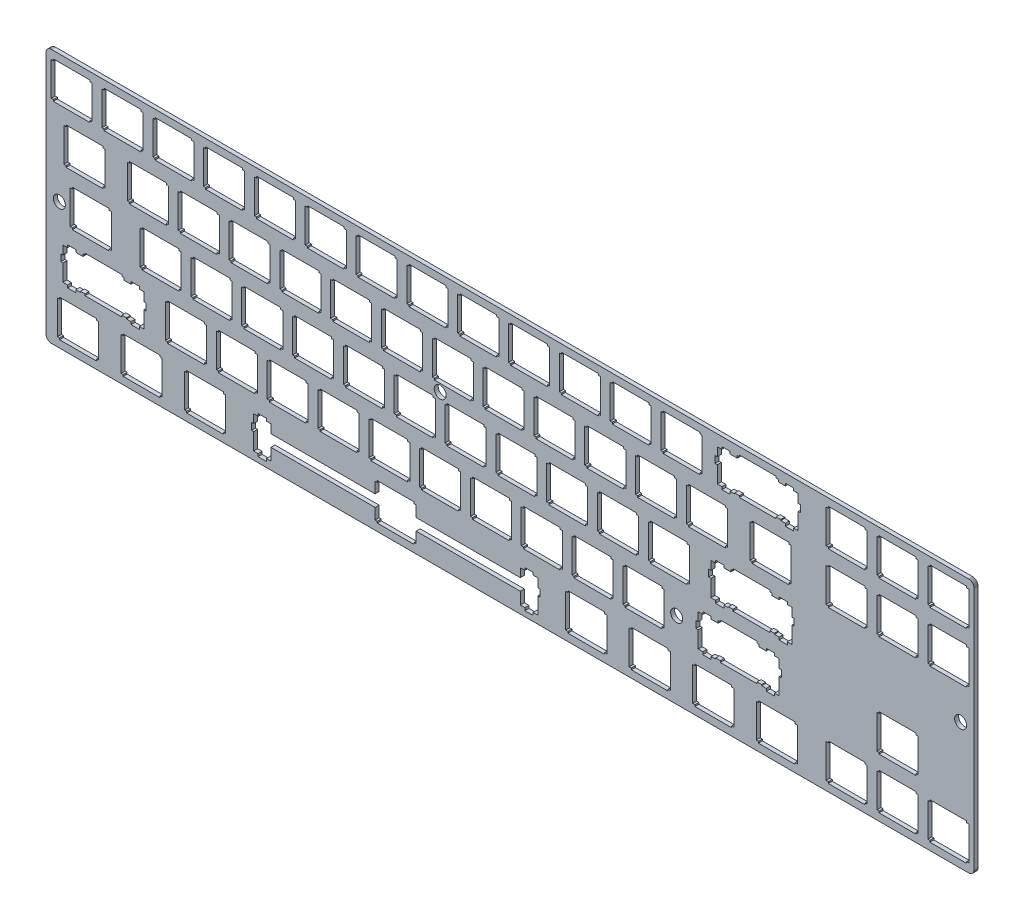
SolidWorks part; units mm, degrees
ref_plane "Front Plane" through (0, 0, 0) normal (0, 0, 1) x (1, 0, 0)
ref_plane "Top Plane" through (0, 0, 0) normal (0, 1, 0) x (1, 0, 0)
ref_plane "Right Plane" through (0, 0, 0) normal (1, 0, 0) x (0, 0, -1)
sketch "Model" plane through (0, 0, 0) normal (0, 0, 1) x (1, 0, 0)
  line L0 (345.958, 95.8603) -> (346.115, 95.8536)
  line L1 (346.115, 95.8536) -> (346.272, 95.8356)
  line L2 (346.272, 95.8356) -> (346.425, 95.8053)
  line L3 (346.425, 95.8053) -> (346.577, 95.7626)
  line L4 (346.577, 95.7626) -> (346.724, 95.7076)
  line L5 (346.724, 95.7076) -> (346.866, 95.6426)
  line L6 (346.866, 95.6426) -> (347.004, 95.5657)
  line L7 (347.004, 95.5657) -> (347.135, 95.4786)
  line L8 (347.135, 95.4786) -> (347.258, 95.3809)
  line L9 (347.258, 95.3809) -> (347.373, 95.2747)
  line L10 (347.373, 95.2747) -> (347.479, 95.159)
  line L11 (347.479, 95.159) -> (347.577, 95.0366)
  line L12 (347.577, 95.0366) -> (347.664, 94.9053)
  line L13 (347.664, 94.9053) -> (347.741, 94.7678)
  line L14 (347.741, 94.7678) -> (347.806, 94.6256)
  line L15 (347.806, 94.6256) -> (347.861, 94.4795)
  line L16 (347.861, 94.4795) -> (347.904, 94.3268)
  line L17 (347.904, 94.3268) -> (347.934, 94.1737)
  line L18 (347.934, 94.1737) -> (347.952, 94.0167)
  line L19 (347.952, 94.0167) -> (347.959, 93.8597)
  line L20 (347.959, 93.8597) -> (347.959, 2.4102)
  line L21 (347.959, 2.4102) -> (347.952, 2.2531)
  line L22 (347.952, 2.2531) -> (347.934, 2.0974)
  line L23 (347.934, 2.0974) -> (347.904, 1.943)
  line L24 (347.904, 1.943) -> (347.861, 1.7914)
  line L25 (347.861, 1.7914) -> (347.806, 1.644)
  line L26 (347.806, 1.644) -> (347.741, 1.5021)
  line L27 (347.741, 1.5021) -> (347.664, 1.3656)
  line L28 (347.664, 1.3656) -> (347.577, 1.2347)
  line L29 (347.577, 1.2347) -> (347.479, 1.1107)
  line L30 (347.479, 1.1107) -> (347.373, 0.9949)
  line L31 (347.373, 0.9949) -> (347.258, 0.8888)
  line L32 (347.258, 0.8888) -> (347.135, 0.791)
  line L33 (347.135, 0.791) -> (347.004, 0.7042)
  line L34 (347.004, 0.7042) -> (346.866, 0.627)
  line L35 (346.866, 0.627) -> (346.724, 0.5622)
  line L36 (346.724, 0.5622) -> (346.577, 0.5071)
  line L37 (346.577, 0.5071) -> (346.425, 0.4644)
  line L38 (346.425, 0.4644) -> (346.272, 0.4341)
  line L39 (346.272, 0.4341) -> (346.115, 0.4162)
  line L40 (346.115, 0.4162) -> (345.958, 0.4107)
  line L41 (345.958, 0.4107) -> (2.096, 0.4107)
  line L42 (2.096, 0.4107) -> (1.9389, 0.4162)
  line L43 (1.9389, 0.4162) -> (1.7818, 0.4341)
  line L44 (1.7818, 0.4341) -> (1.6288, 0.4644)
  line L45 (1.6288, 0.4644) -> (1.4759, 0.5071)
  line L46 (1.4759, 0.5071) -> (1.3298, 0.5622)
  line L47 (1.3298, 0.5622) -> (1.1879, 0.627)
  line L48 (1.1879, 0.627) -> (1.0501, 0.7042)
  line L49 (1.0501, 0.7042) -> (0.9192, 0.791)
  line L50 (0.9192, 0.791) -> (0.7965, 0.8888)
  line L51 (0.7965, 0.8888) -> (0.6808, 0.9949)
  line L52 (0.6808, 0.9949) -> (0.5746, 1.1107)
  line L53 (0.5746, 1.1107) -> (0.4768, 1.2347)
  line L54 (0.4768, 1.2347) -> (0.39, 1.3656)
  line L55 (0.39, 1.3656) -> (0.3128, 1.5021)
  line L56 (0.3128, 1.5021) -> (0.248, 1.644)
  line L57 (0.248, 1.644) -> (0.1929, 1.7914)
  line L58 (0.1929, 1.7914) -> (0.1502, 1.943)
  line L59 (0.1502, 1.943) -> (0.1199, 2.0974)
  line L60 (0.1199, 2.0974) -> (0.102, 2.2531)
  line L61 (0.102, 2.2531) -> (0.0951, 2.4088)
  line L62 (0.0951, 2.4088) -> (0.0951, 93.8597)
  line L63 (0.0951, 93.8597) -> (0.102, 94.0167)
  line L64 (0.102, 94.0167) -> (0.1199, 94.1737)
  line L65 (0.1199, 94.1737) -> (0.1502, 94.3268)
  line L66 (0.1502, 94.3268) -> (0.1929, 94.4795)
  line L67 (0.1929, 94.4795) -> (0.248, 94.6256)
  line L68 (0.248, 94.6256) -> (0.3128, 94.7678)
  line L69 (0.3128, 94.7678) -> (0.39, 94.9053)
  line L70 (0.39, 94.9053) -> (0.4768, 95.0366)
  line L71 (0.4768, 95.0366) -> (0.5746, 95.159)
  line L72 (0.5746, 95.159) -> (0.6808, 95.2747)
  line L73 (0.6808, 95.2747) -> (0.7965, 95.3809)
  line L74 (0.7965, 95.3809) -> (0.9192, 95.4786)
  line L75 (0.9192, 95.4786) -> (1.0501, 95.5657)
  line L76 (1.0501, 95.5657) -> (1.1879, 95.6426)
  line L77 (1.1879, 95.6426) -> (1.3298, 95.7076)
  line L78 (1.3298, 95.7076) -> (1.4759, 95.7626)
  line L79 (1.4759, 95.7626) -> (1.6288, 95.8053)
  line L80 (1.6288, 95.8053) -> (1.7818, 95.8356)
  line L81 (1.7818, 95.8356) -> (1.9389, 95.8536)
  line L82 (1.9389, 95.8536) -> (2.096, 95.8603)
  line L83 (2.096, 95.8603) -> (345.958, 95.8603)
  line L84 (124.263, 16.9361) -> (124.263, 16.3366)
  line L85 (124.263, 16.3366) -> (123.464, 16.3366)
  line L86 (123.464, 16.3366) -> (123.464, 12.2356)
  line L87 (123.464, 12.2356) -> (84.4381, 12.2356)
  line L88 (84.4381, 12.2356) -> (84.4381, 15.4657)
  line L89 (84.4381, 15.4657) -> (82.714, 15.4657)
  line L90 (82.714, 15.4657) -> (82.714, 16.3849)
  line L91 (82.714, 16.3849) -> (79.6135, 16.3849)
  line L92 (79.6135, 16.3849) -> (79.6135, 15.4657)
  line L93 (79.6135, 15.4657) -> (77.888, 15.4657)
  line L94 (77.888, 15.4657) -> (77.888, 12.2356)
  line L95 (77.888, 12.2356) -> (77.064, 12.2356)
  line L96 (77.064, 12.2356) -> (77.064, 9.6352)
  line L97 (77.064, 9.6352) -> (77.888, 9.6352)
  line L98 (77.888, 9.6352) -> (77.888, 3.3666)
  line L99 (77.888, 3.3666) -> (79.6135, 3.3666)
  line L100 (79.6135, 3.3666) -> (79.6135, 2.3854)
  line L101 (79.6135, 2.3854) -> (82.714, 2.3854)
  line L102 (82.714, 2.3854) -> (82.714, 3.3666)
  line L103 (82.714, 3.3666) -> (84.4381, 3.3666)
  line L104 (84.4381, 3.3666) -> (84.4381, 7.8355)
  line L105 (84.4381, 7.8355) -> (123.464, 7.8355)
  line L106 (123.464, 7.8355) -> (123.464, 3.7359)
  line L107 (123.464, 3.7359) -> (124.263, 3.7359)
  line L108 (124.263, 3.7359) -> (124.263, 3.135)
  line L109 (124.263, 3.135) -> (138.063, 3.135)
  line L110 (138.063, 3.135) -> (138.063, 3.7359)
  line L111 (138.063, 3.7359) -> (138.864, 3.7359)
  line L112 (138.864, 3.7359) -> (138.864, 7.8355)
  line L113 (138.864, 7.8355) -> (177.888, 7.8355)
  line L114 (177.888, 7.8355) -> (177.888, 3.3666)
  line L115 (177.888, 3.3666) -> (179.614, 3.3666)
  line L116 (179.614, 3.3666) -> (179.614, 2.3854)
  line L117 (179.614, 2.3854) -> (182.714, 2.3854)
  line L118 (182.714, 2.3854) -> (182.714, 3.3666)
  line L119 (182.714, 3.3666) -> (184.438, 3.3666)
  line L120 (184.438, 3.3666) -> (184.438, 9.6352)
  line L121 (184.438, 9.6352) -> (185.263, 9.6352)
  line L122 (185.263, 9.6352) -> (185.263, 12.2356)
  line L123 (185.263, 12.2356) -> (184.438, 12.2356)
  line L124 (184.438, 12.2356) -> (184.438, 15.4657)
  line L125 (184.438, 15.4657) -> (182.714, 15.4657)
  line L126 (182.714, 15.4657) -> (182.714, 16.3849)
  line L127 (182.714, 16.3849) -> (179.614, 16.3849)
  line L128 (179.614, 16.3849) -> (179.614, 15.4657)
  line L129 (179.614, 15.4657) -> (177.888, 15.4657)
  line L130 (177.888, 15.4657) -> (177.888, 12.2356)
  line L131 (177.888, 12.2356) -> (138.864, 12.2356)
  line L132 (138.864, 12.2356) -> (138.864, 16.3366)
  line L133 (138.864, 16.3366) -> (138.063, 16.3366)
  line L134 (138.063, 16.3366) -> (138.063, 16.9361)
  line L135 (138.063, 16.9361) -> (124.263, 16.9361)
  line L136 (331.432, 16.9361) -> (331.432, 16.3366)
  line L137 (331.432, 16.3366) -> (330.633, 16.3366)
  line L138 (330.633, 16.3366) -> (330.633, 3.7359)
  line L139 (330.633, 3.7359) -> (331.432, 3.7359)
  line L140 (331.432, 3.7359) -> (331.432, 3.135)
  line L141 (331.432, 3.135) -> (345.233, 3.135)
  line L142 (345.233, 3.135) -> (345.233, 3.7359)
  line L143 (345.233, 3.7359) -> (346.032, 3.7359)
  line L144 (346.032, 3.7359) -> (346.032, 16.3366)
  line L145 (346.032, 16.3366) -> (345.233, 16.3366)
  line L146 (345.233, 16.3366) -> (345.233, 16.9361)
  line L147 (345.233, 16.9361) -> (331.432, 16.9361)
  line L148 (312.382, 16.9361) -> (312.382, 16.3366)
  line L149 (312.382, 16.3366) -> (311.583, 16.3366)
  line L150 (311.583, 16.3366) -> (311.583, 3.7359)
  line L151 (311.583, 3.7359) -> (312.382, 3.7359)
  line L152 (312.382, 3.7359) -> (312.382, 3.135)
  line L153 (312.382, 3.135) -> (326.183, 3.135)
  line L154 (326.183, 3.135) -> (326.183, 3.7359)
  line L155 (326.183, 3.7359) -> (326.982, 3.7359)
  line L156 (326.982, 3.7359) -> (326.982, 16.3366)
  line L157 (326.982, 16.3366) -> (326.183, 16.3366)
  line L158 (326.183, 16.3366) -> (326.183, 16.9361)
  line L159 (326.183, 16.9361) -> (312.382, 16.9361)
  line L160 (293.332, 16.9361) -> (293.332, 16.3366)
  line L161 (293.332, 16.3366) -> (292.533, 16.3366)
  line L162 (292.533, 16.3366) -> (292.533, 3.7359)
  line L163 (292.533, 3.7359) -> (293.332, 3.7359)
  line L164 (293.332, 3.7359) -> (293.332, 3.135)
  line L165 (293.332, 3.135) -> (307.133, 3.135)
  line L166 (307.133, 3.135) -> (307.133, 3.7359)
  line L167 (307.133, 3.7359) -> (307.932, 3.7359)
  line L168 (307.932, 3.7359) -> (307.932, 16.3366)
  line L169 (307.932, 16.3366) -> (307.133, 16.3366)
  line L170 (307.133, 16.3366) -> (307.133, 16.9361)
  line L171 (307.133, 16.9361) -> (293.332, 16.9361)
  line L172 (267.138, 16.9361) -> (267.138, 16.3366)
  line L173 (267.138, 16.3366) -> (266.339, 16.3366)
  line L174 (266.339, 16.3366) -> (266.339, 3.7359)
  line L175 (266.339, 3.7359) -> (267.138, 3.7359)
  line L176 (267.138, 3.7359) -> (267.138, 3.135)
  line L177 (267.138, 3.135) -> (280.938, 3.135)
  line L178 (280.938, 3.135) -> (280.938, 3.7359)
  line L179 (280.938, 3.7359) -> (281.739, 3.7359)
  line L180 (281.739, 3.7359) -> (281.739, 16.3366)
  line L181 (281.739, 16.3366) -> (280.938, 16.3366)
  line L182 (280.938, 16.3366) -> (280.938, 16.9361)
  line L183 (280.938, 16.9361) -> (267.138, 16.9361)
  line L184 (243.327, 16.9361) -> (243.327, 16.3366)
  line L185 (243.327, 16.3366) -> (242.527, 16.3366)
  line L186 (242.527, 16.3366) -> (242.527, 3.7359)
  line L187 (242.527, 3.7359) -> (243.327, 3.7359)
  line L188 (243.327, 3.7359) -> (243.327, 3.135)
  line L189 (243.327, 3.135) -> (257.127, 3.135)
  line L190 (257.127, 3.135) -> (257.127, 3.7359)
  line L191 (257.127, 3.7359) -> (257.926, 3.7359)
  line L192 (257.926, 3.7359) -> (257.926, 16.3366)
  line L193 (257.926, 16.3366) -> (257.127, 16.3366)
  line L194 (257.127, 16.3366) -> (257.127, 16.9361)
  line L195 (257.127, 16.9361) -> (243.327, 16.9361)
  line L196 (219.513, 16.9361) -> (219.513, 16.3366)
  line L197 (219.513, 16.3366) -> (218.714, 16.3366)
  line L198 (218.714, 16.3366) -> (218.714, 3.7359)
  line L199 (218.714, 3.7359) -> (219.513, 3.7359)
  line L200 (219.513, 3.7359) -> (219.513, 3.135)
  line L201 (219.513, 3.135) -> (233.313, 3.135)
  line L202 (233.313, 3.135) -> (233.313, 3.7359)
  line L203 (233.313, 3.7359) -> (234.114, 3.7359)
  line L204 (234.114, 3.7359) -> (234.114, 16.3366)
  line L205 (234.114, 16.3366) -> (233.313, 16.3366)
  line L206 (233.313, 16.3366) -> (233.313, 16.9361)
  line L207 (233.313, 16.9361) -> (219.513, 16.9361)
  line L208 (195.702, 16.9361) -> (195.702, 16.3366)
  line L209 (195.702, 16.3366) -> (194.902, 16.3366)
  line L210 (194.902, 16.3366) -> (194.902, 3.7359)
  line L211 (194.902, 3.7359) -> (195.702, 3.7359)
  line L212 (195.702, 3.7359) -> (195.702, 3.135)
  line L213 (195.702, 3.135) -> (209.502, 3.135)
  line L214 (209.502, 3.135) -> (209.502, 3.7359)
  line L215 (209.502, 3.7359) -> (210.301, 3.7359)
  line L216 (210.301, 3.7359) -> (210.301, 16.3366)
  line L217 (210.301, 16.3366) -> (209.502, 16.3366)
  line L218 (209.502, 16.3366) -> (209.502, 16.9361)
  line L219 (209.502, 16.9361) -> (195.702, 16.9361)
  line L220 (52.8271, 16.9361) -> (52.8271, 16.3366)
  line L221 (52.8271, 16.3366) -> (52.0266, 16.3366)
  line L222 (52.0266, 16.3366) -> (52.0266, 3.7359)
  line L223 (52.0266, 3.7359) -> (52.8271, 3.7359)
  line L224 (52.8271, 3.7359) -> (52.8271, 3.135)
  line L225 (52.8271, 3.135) -> (66.6267, 3.135)
  line L226 (66.6267, 3.135) -> (66.6267, 3.7359)
  line L227 (66.6267, 3.7359) -> (67.4261, 3.7359)
  line L228 (67.4261, 3.7359) -> (67.4261, 16.3366)
  line L229 (67.4261, 16.3366) -> (66.6267, 16.3366)
  line L230 (66.6267, 16.3366) -> (66.6267, 16.9361)
  line L231 (66.6267, 16.9361) -> (52.8271, 16.9361)
  line L232 (29.0132, 16.9361) -> (29.0132, 16.3366)
  line L233 (29.0132, 16.3366) -> (28.214, 16.3366)
  line L234 (28.214, 16.3366) -> (28.214, 3.7359)
  line L235 (28.214, 3.7359) -> (29.0132, 3.7359)
  line L236 (29.0132, 3.7359) -> (29.0132, 3.135)
  line L237 (29.0132, 3.135) -> (42.8128, 3.135)
  line L238 (42.8128, 3.135) -> (42.8128, 3.7359)
  line L239 (42.8128, 3.7359) -> (43.6136, 3.7359)
  line L240 (43.6136, 3.7359) -> (43.6136, 16.3366)
  line L241 (43.6136, 16.3366) -> (42.8128, 16.3366)
  line L242 (42.8128, 16.3366) -> (42.8128, 16.9361)
  line L243 (42.8128, 16.9361) -> (29.0132, 16.9361)
  line L244 (5.2021, 16.9361) -> (5.2021, 16.3366)
  line L245 (5.2021, 16.3366) -> (4.4015, 16.3366)
  line L246 (4.4015, 16.3366) -> (4.4015, 3.7359)
  line L247 (4.4015, 3.7359) -> (5.2021, 3.7359)
  line L248 (5.2021, 3.7359) -> (5.2021, 3.135)
  line L249 (5.2021, 3.135) -> (19.0018, 3.135)
  line L250 (19.0018, 3.135) -> (19.0018, 3.7359)
  line L251 (19.0018, 3.7359) -> (19.801, 3.7359)
  line L252 (19.801, 3.7359) -> (19.801, 16.3366)
  line L253 (19.801, 16.3366) -> (19.0018, 16.3366)
  line L254 (19.0018, 16.3366) -> (19.0018, 16.9361)
  line L255 (19.0018, 16.9361) -> (5.2021, 16.9361)
  line L256 (252.851, 35.9876) -> (252.851, 35.3868)
  line L257 (252.851, 35.3868) -> (252.052, 35.3868)
  line L258 (252.052, 35.3868) -> (252.052, 34.5157)
  line L259 (267.451, 34.5157) -> (268.377, 34.5157)
  line L260 (272.214, 53.5658) -> (273.138, 53.5658)
  line L261 (251.127, 34.5157) -> (249.402, 34.5157)
  line L262 (249.402, 34.5157) -> (249.402, 35.4348)
  line L263 (249.402, 35.4348) -> (246.301, 35.4348)
  line L264 (246.301, 35.4348) -> (246.301, 34.5157)
  line L265 (246.301, 34.5157) -> (244.577, 34.5157)
  line L266 (244.577, 34.5157) -> (244.577, 31.2856)
  line L267 (244.577, 31.2856) -> (243.751, 31.2856)
  line L268 (243.751, 31.2856) -> (243.751, 28.6852)
  line L269 (243.751, 28.6852) -> (244.577, 28.6852)
  line L270 (244.577, 28.6852) -> (244.577, 22.4152)
  line L271 (244.577, 22.4152) -> (246.301, 22.4152)
  line L272 (246.301, 22.4152) -> (246.301, 21.4354)
  line L273 (246.301, 21.4354) -> (249.402, 21.4354)
  line L274 (249.402, 21.4354) -> (249.402, 22.4152)
  line L275 (249.402, 22.4152) -> (251.127, 22.4152)
  line L276 (251.127, 22.4152) -> (251.127, 22.7858)
  line L277 (29.326, 34.5157) -> (30.2521, 34.5157)
  line L279 (252.052, 22.7858) -> (252.851, 22.7858)
  line L280 (252.851, 22.7858) -> (252.851, 22.185)
  line L281 (252.851, 22.185) -> (266.652, 22.185)
  line L282 (266.652, 22.185) -> (266.652, 22.7858)
  line L283 (266.652, 22.7858) -> (267.451, 22.7858)
  line L286 (268.377, 22.7858) -> (268.377, 22.4152)
  line L287 (268.377, 22.4152) -> (270.101, 22.4152)
  line L288 (270.101, 22.4152) -> (270.101, 21.4354)
  line L289 (270.101, 21.4354) -> (273.202, 21.4354)
  line L290 (273.202, 21.4354) -> (273.202, 22.4152)
  line L291 (273.202, 22.4152) -> (274.927, 22.4152)
  line L292 (274.927, 22.4152) -> (274.927, 28.6852)
  line L293 (274.927, 28.6852) -> (275.751, 28.6852)
  line L294 (275.751, 28.6852) -> (275.751, 31.2856)
  line L295 (275.751, 31.2856) -> (274.927, 31.2856)
  line L296 (274.927, 31.2856) -> (274.927, 34.5157)
  line L297 (274.927, 34.5157) -> (273.202, 34.5157)
  line L298 (273.202, 34.5157) -> (273.202, 35.4348)
  line L299 (273.202, 35.4348) -> (270.101, 35.4348)
  line L300 (270.101, 35.4348) -> (270.101, 34.5157)
  line L301 (270.101, 34.5157) -> (268.377, 34.5157)
  line L304 (267.451, 34.5157) -> (267.451, 35.3868)
  line L305 (267.451, 35.3868) -> (266.652, 35.3868)
  line L306 (266.652, 35.3868) -> (266.652, 35.9876)
  line L307 (266.652, 35.9876) -> (252.851, 35.9876)
  line L308 (14.7271, 35.9876) -> (14.7271, 35.3868)
  line L309 (14.7271, 35.3868) -> (13.9265, 35.3868)
  line L310 (13.9265, 35.3868) -> (13.9265, 34.5157)
  line L313 (13.0018, 34.5157) -> (11.2765, 34.5157)
  line L314 (11.2765, 34.5157) -> (11.2765, 35.4348)
  line L315 (11.2765, 35.4348) -> (8.1759, 35.4348)
  line L316 (8.1759, 35.4348) -> (8.1759, 34.5157)
  line L317 (8.1759, 34.5157) -> (6.452, 34.5157)
  line L318 (6.452, 34.5157) -> (6.452, 31.2856)
  line L319 (6.452, 31.2856) -> (5.6265, 31.2856)
  line L320 (5.6265, 31.2856) -> (5.6265, 28.6852)
  line L321 (5.6265, 28.6852) -> (6.452, 28.6852)
  line L322 (6.452, 28.6852) -> (6.452, 22.4152)
  line L323 (6.452, 22.4152) -> (8.1759, 22.4152)
  line L324 (8.1759, 22.4152) -> (8.1759, 21.4354)
  line L325 (8.1759, 21.4354) -> (11.2765, 21.4354)
  line L326 (11.2765, 21.4354) -> (11.2765, 22.4152)
  line L327 (11.2765, 22.4152) -> (13.0018, 22.4152)
  line L328 (13.0018, 22.4152) -> (13.0018, 22.7858)
  line L331 (13.9265, 22.7858) -> (14.7271, 22.7858)
  line L332 (14.7271, 22.7858) -> (14.7271, 22.185)
  line L333 (14.7271, 22.185) -> (28.5268, 22.185)
  line L334 (28.5268, 22.185) -> (28.5268, 22.7858)
  line L335 (28.5268, 22.7858) -> (29.326, 22.7858)
  line L338 (30.2521, 22.7858) -> (30.2521, 22.4152)
  line L339 (30.2521, 22.4152) -> (31.976, 22.4152)
  line L340 (31.976, 22.4152) -> (31.976, 21.4354)
  line L341 (31.976, 21.4354) -> (35.0766, 21.4354)
  line L342 (35.0766, 21.4354) -> (35.0766, 22.4152)
  line L343 (35.0766, 22.4152) -> (36.8018, 22.4152)
  line L344 (36.8018, 22.4152) -> (36.8018, 28.6852)
  line L345 (36.8018, 28.6852) -> (37.6259, 28.6852)
  line L346 (37.6259, 28.6852) -> (37.6259, 31.2856)
  line L347 (37.6259, 31.2856) -> (36.8018, 31.2856)
  line L348 (36.8018, 31.2856) -> (36.8018, 34.5157)
  line L349 (36.8018, 34.5157) -> (35.0766, 34.5157)
  line L350 (35.0766, 34.5157) -> (35.0766, 35.4348)
  line L351 (35.0766, 35.4348) -> (31.976, 35.4348)
  line L352 (31.976, 35.4348) -> (31.976, 34.5157)
  line L353 (31.976, 34.5157) -> (30.2521, 34.5157)
  line L356 (29.326, 34.5157) -> (29.326, 35.3868)
  line L357 (29.326, 35.3868) -> (28.5268, 35.3868)
  line L358 (28.5268, 35.3868) -> (28.5268, 35.9876)
  line L359 (28.5268, 35.9876) -> (14.7271, 35.9876)
  line L360 (312.382, 35.9876) -> (312.382, 35.3868)
  line L361 (312.382, 35.3868) -> (311.583, 35.3868)
  line L362 (311.583, 35.3868) -> (311.583, 22.7858)
  line L363 (311.583, 22.7858) -> (312.382, 22.7858)
  line L364 (312.382, 22.7858) -> (312.382, 22.185)
  line L365 (312.382, 22.185) -> (326.183, 22.185)
  line L366 (326.183, 22.185) -> (326.183, 22.7858)
  line L367 (326.183, 22.7858) -> (326.982, 22.7858)
  line L368 (326.982, 22.7858) -> (326.982, 35.3868)
  line L369 (326.982, 35.3868) -> (326.183, 35.3868)
  line L370 (326.183, 35.3868) -> (326.183, 35.9876)
  line L371 (326.183, 35.9876) -> (312.382, 35.9876)
  line L372 (217.132, 35.9876) -> (217.132, 35.3868)
  line L373 (217.132, 35.3868) -> (216.333, 35.3868)
  line L374 (216.333, 35.3868) -> (216.333, 22.7858)
  line L375 (216.333, 22.7858) -> (217.132, 22.7858)
  line L376 (217.132, 22.7858) -> (217.132, 22.185)
  line L377 (217.132, 22.185) -> (230.933, 22.185)
  line L378 (230.933, 22.185) -> (230.933, 22.7858)
  line L379 (230.933, 22.7858) -> (231.732, 22.7858)
  line L380 (231.732, 22.7858) -> (231.732, 35.3868)
  line L381 (231.732, 35.3868) -> (230.933, 35.3868)
  line L382 (230.933, 35.3868) -> (230.933, 35.9876)
  line L383 (230.933, 35.9876) -> (217.132, 35.9876)
  line L384 (198.082, 35.9876) -> (198.082, 35.3868)
  line L385 (198.082, 35.3868) -> (197.283, 35.3868)
  line L386 (197.283, 35.3868) -> (197.283, 22.7858)
  line L387 (197.283, 22.7858) -> (198.082, 22.7858)
  line L388 (198.082, 22.7858) -> (198.082, 22.185)
  line L389 (198.082, 22.185) -> (211.883, 22.185)
  line L390 (211.883, 22.185) -> (211.883, 22.7858)
  line L391 (211.883, 22.7858) -> (212.682, 22.7858)
  line L392 (212.682, 22.7858) -> (212.682, 35.3868)
  line L393 (212.682, 35.3868) -> (211.883, 35.3868)
  line L394 (211.883, 35.3868) -> (211.883, 35.9876)
  line L395 (211.883, 35.9876) -> (198.082, 35.9876)
  line L396 (179.032, 35.9876) -> (179.032, 35.3868)
  line L397 (179.032, 35.3868) -> (178.233, 35.3868)
  line L398 (178.233, 35.3868) -> (178.233, 22.7858)
  line L399 (178.233, 22.7858) -> (179.032, 22.7858)
  line L400 (179.032, 22.7858) -> (179.032, 22.185)
  line L401 (179.032, 22.185) -> (192.833, 22.185)
  line L402 (192.833, 22.185) -> (192.833, 22.7858)
  line L403 (192.833, 22.7858) -> (193.632, 22.7858)
  line L404 (193.632, 22.7858) -> (193.632, 35.3868)
  line L405 (193.632, 35.3868) -> (192.833, 35.3868)
  line L406 (192.833, 35.3868) -> (192.833, 35.9876)
  line L407 (192.833, 35.9876) -> (179.032, 35.9876)
  line L408 (159.982, 35.9876) -> (159.982, 35.3868)
  line L409 (159.982, 35.3868) -> (159.183, 35.3868)
  line L410 (159.183, 35.3868) -> (159.183, 22.7858)
  line L411 (159.183, 22.7858) -> (159.982, 22.7858)
  line L412 (159.982, 22.7858) -> (159.982, 22.185)
  line L413 (159.982, 22.185) -> (173.783, 22.185)
  line L414 (173.783, 22.185) -> (173.783, 22.7858)
  line L415 (173.783, 22.7858) -> (174.582, 22.7858)
  line L416 (174.582, 22.7858) -> (174.582, 35.3868)
  line L417 (174.582, 35.3868) -> (173.783, 35.3868)
  line L418 (173.783, 35.3868) -> (173.783, 35.9876)
  line L419 (173.783, 35.9876) -> (159.982, 35.9876)
  line L420 (140.932, 35.9876) -> (140.932, 35.3868)
  line L421 (140.932, 35.3868) -> (140.133, 35.3868)
  line L422 (140.133, 35.3868) -> (140.133, 22.7858)
  line L423 (140.133, 22.7858) -> (140.932, 22.7858)
  line L424 (140.932, 22.7858) -> (140.932, 22.185)
  line L425 (140.932, 22.185) -> (154.733, 22.185)
  line L426 (154.733, 22.185) -> (154.733, 22.7858)
  line L427 (154.733, 22.7858) -> (155.532, 22.7858)
  line L428 (155.532, 22.7858) -> (155.532, 35.3868)
  line L429 (155.532, 35.3868) -> (154.733, 35.3868)
  line L430 (154.733, 35.3868) -> (154.733, 35.9876)
  line L431 (154.733, 35.9876) -> (140.932, 35.9876)
  line L432 (121.882, 35.9876) -> (121.882, 35.3868)
  line L433 (121.882, 35.3868) -> (121.083, 35.3868)
  line L434 (121.083, 35.3868) -> (121.083, 22.7858)
  line L435 (121.083, 22.7858) -> (121.882, 22.7858)
  line L436 (121.882, 22.7858) -> (121.882, 22.185)
  line L437 (121.882, 22.185) -> (135.683, 22.185)
  line L438 (135.683, 22.185) -> (135.683, 22.7858)
  line L439 (135.683, 22.7858) -> (136.482, 22.7858)
  line L440 (136.482, 22.7858) -> (136.482, 35.3868)
  line L441 (136.482, 35.3868) -> (135.683, 35.3868)
  line L442 (135.683, 35.3868) -> (135.683, 35.9876)
  line L443 (135.683, 35.9876) -> (121.882, 35.9876)
  line L444 (102.832, 35.9876) -> (102.832, 35.3868)
  line L445 (102.832, 35.3868) -> (102.033, 35.3868)
  line L446 (102.033, 35.3868) -> (102.033, 22.7858)
  line L447 (102.033, 22.7858) -> (102.832, 22.7858)
  line L448 (102.832, 22.7858) -> (102.832, 22.185)
  line L449 (102.832, 22.185) -> (116.633, 22.185)
  line L450 (116.633, 22.185) -> (116.633, 22.7858)
  line L451 (116.633, 22.7858) -> (117.432, 22.7858)
  line L452 (117.432, 22.7858) -> (117.432, 35.3868)
  line L453 (117.432, 35.3868) -> (116.633, 35.3868)
  line L454 (116.633, 35.3868) -> (116.633, 35.9876)
  line L455 (116.633, 35.9876) -> (102.832, 35.9876)
  line L456 (83.7819, 35.9876) -> (83.7819, 35.3868)
  line L457 (83.7819, 35.3868) -> (82.9829, 35.3868)
  line L458 (82.9829, 35.3868) -> (82.9829, 22.7858)
  line L459 (82.9829, 22.7858) -> (83.7819, 22.7858)
  line L460 (83.7819, 22.7858) -> (83.7819, 22.185)
  line L461 (83.7819, 22.185) -> (97.5829, 22.185)
  line L462 (97.5829, 22.185) -> (97.5829, 22.7858)
  line L463 (97.5829, 22.7858) -> (98.3823, 22.7858)
  line L464 (98.3823, 22.7858) -> (98.3823, 35.3868)
  line L465 (98.3823, 35.3868) -> (97.5829, 35.3868)
  line L466 (97.5829, 35.3868) -> (97.5829, 35.9876)
  line L467 (97.5829, 35.9876) -> (83.7819, 35.9876)
  line L468 (64.7319, 35.9876) -> (64.7319, 35.3868)
  line L469 (64.7319, 35.3868) -> (63.9329, 35.3868)
  line L470 (63.9329, 35.3868) -> (63.9329, 22.7858)
  line L471 (63.9329, 22.7858) -> (64.7319, 22.7858)
  line L472 (64.7319, 22.7858) -> (64.7319, 22.185)
  line L473 (64.7319, 22.185) -> (78.5329, 22.185)
  line L474 (78.5329, 22.185) -> (78.5329, 22.7858)
  line L475 (78.5329, 22.7858) -> (79.3323, 22.7858)
  line L476 (79.3323, 22.7858) -> (79.3323, 35.3868)
  line L477 (79.3323, 35.3868) -> (78.5329, 35.3868)
  line L478 (78.5329, 35.3868) -> (78.5329, 35.9876)
  line L479 (78.5329, 35.9876) -> (64.7319, 35.9876)
  line L480 (45.6819, 35.9876) -> (45.6819, 35.3868)
  line L481 (45.6819, 35.3868) -> (44.8829, 35.3868)
  line L482 (44.8829, 35.3868) -> (44.8829, 22.7858)
  line L483 (44.8829, 22.7858) -> (45.6819, 22.7858)
  line L484 (45.6819, 22.7858) -> (45.6819, 22.185)
  line L485 (45.6819, 22.185) -> (59.4829, 22.185)
  line L486 (59.4829, 22.185) -> (59.4829, 22.7858)
  line L487 (59.4829, 22.7858) -> (60.2823, 22.7858)
  line L488 (60.2823, 22.7858) -> (60.2823, 35.3868)
  line L489 (60.2823, 35.3868) -> (59.4829, 35.3868)
  line L490 (59.4829, 35.3868) -> (59.4829, 35.9876)
  line L491 (59.4829, 35.9876) -> (45.6819, 35.9876)
  line L492 (257.613, 55.0362) -> (257.613, 54.4354)
  line L493 (257.613, 54.4354) -> (256.814, 54.4354)
  line L494 (256.814, 54.4354) -> (256.814, 53.5658)
  line L497 (255.888, 53.5658) -> (254.163, 53.5658)
  line L498 (254.163, 53.5658) -> (254.163, 54.4862)
  line L499 (254.163, 54.4862) -> (251.063, 54.4862)
  line L500 (251.063, 54.4862) -> (251.063, 53.5658)
  line L501 (251.063, 53.5658) -> (249.338, 53.5658)
  line L502 (249.338, 53.5658) -> (249.338, 50.3357)
  line L503 (249.338, 50.3357) -> (248.514, 50.3357)
  line L504 (248.514, 50.3357) -> (248.514, 47.7365)
  line L505 (248.514, 47.7365) -> (249.338, 47.7365)
  line L506 (249.338, 47.7365) -> (249.338, 41.4666)
  line L507 (249.338, 41.4666) -> (251.063, 41.4666)
  line L508 (251.063, 41.4666) -> (251.063, 40.4855)
  line L509 (251.063, 40.4855) -> (254.163, 40.4855)
  line L510 (254.163, 40.4855) -> (254.163, 41.4666)
  line L511 (254.163, 41.4666) -> (255.888, 41.4666)
  line L512 (255.888, 41.4666) -> (255.888, 41.8359)
  line L515 (256.814, 41.8359) -> (257.613, 41.8359)
  line L516 (257.613, 41.8359) -> (257.613, 41.2365)
  line L517 (257.613, 41.2365) -> (271.413, 41.2365)
  line L518 (271.413, 41.2365) -> (271.413, 41.8359)
  line L519 (271.413, 41.8359) -> (272.214, 41.8359)
  line L522 (273.138, 41.8359) -> (273.138, 41.4666)
  line L523 (273.138, 41.4666) -> (274.864, 41.4666)
  line L524 (274.864, 41.4666) -> (274.864, 40.4855)
  line L525 (274.864, 40.4855) -> (277.964, 40.4855)
  line L526 (277.964, 40.4855) -> (277.964, 41.4666)
  line L527 (277.964, 41.4666) -> (279.688, 41.4666)
  line L528 (279.688, 41.4666) -> (279.688, 47.7365)
  line L529 (279.688, 47.7365) -> (280.513, 47.7365)
  line L530 (280.513, 47.7365) -> (280.513, 50.3357)
  line L531 (280.513, 50.3357) -> (279.688, 50.3357)
  line L532 (279.688, 50.3357) -> (279.688, 53.5658)
  line L533 (279.688, 53.5658) -> (277.964, 53.5658)
  line L534 (277.964, 53.5658) -> (277.964, 54.4862)
  line L535 (277.964, 54.4862) -> (274.864, 54.4862)
  line L536 (274.864, 54.4862) -> (274.864, 53.5658)
  line L537 (274.864, 53.5658) -> (273.138, 53.5658)
  line L540 (272.214, 53.5658) -> (272.214, 54.4354)
  line L541 (272.214, 54.4354) -> (271.413, 54.4354)
  line L542 (271.413, 54.4354) -> (271.413, 55.0362)
  line L543 (271.413, 55.0362) -> (257.613, 55.0362)
  line L544 (226.657, 55.0362) -> (226.657, 54.4354)
  line L545 (226.657, 54.4354) -> (225.858, 54.4354)
  line L546 (225.858, 54.4354) -> (225.858, 41.8359)
  line L547 (225.858, 41.8359) -> (226.657, 41.8359)
  line L548 (226.657, 41.8359) -> (226.657, 41.2365)
  line L549 (226.657, 41.2365) -> (240.458, 41.2365)
  line L550 (240.458, 41.2365) -> (240.458, 41.8359)
  line L551 (240.458, 41.8359) -> (241.257, 41.8359)
  line L552 (241.257, 41.8359) -> (241.257, 54.4354)
  line L553 (241.257, 54.4354) -> (240.458, 54.4354)
  line L554 (240.458, 54.4354) -> (240.458, 55.0362)
  line L555 (240.458, 55.0362) -> (226.657, 55.0362)
  line L556 (207.607, 55.0362) -> (207.607, 54.4354)
  line L557 (207.607, 54.4354) -> (206.808, 54.4354)
  line L558 (206.808, 54.4354) -> (206.808, 41.8359)
  line L559 (206.808, 41.8359) -> (207.607, 41.8359)
  line L560 (207.607, 41.8359) -> (207.607, 41.2365)
  line L561 (207.607, 41.2365) -> (221.408, 41.2365)
  line L562 (221.408, 41.2365) -> (221.408, 41.8359)
  line L563 (221.408, 41.8359) -> (222.207, 41.8359)
  line L564 (222.207, 41.8359) -> (222.207, 54.4354)
  line L565 (222.207, 54.4354) -> (221.408, 54.4354)
  line L566 (221.408, 54.4354) -> (221.408, 55.0362)
  line L567 (221.408, 55.0362) -> (207.607, 55.0362)
  line L568 (188.557, 55.0362) -> (188.557, 54.4354)
  line L569 (188.557, 54.4354) -> (187.758, 54.4354)
  line L570 (187.758, 54.4354) -> (187.758, 41.8359)
  line L571 (187.758, 41.8359) -> (188.557, 41.8359)
  line L572 (188.557, 41.8359) -> (188.557, 41.2365)
  line L573 (188.557, 41.2365) -> (202.358, 41.2365)
  line L574 (202.358, 41.2365) -> (202.358, 41.8359)
  line L575 (202.358, 41.8359) -> (203.157, 41.8359)
  line L576 (203.157, 41.8359) -> (203.157, 54.4354)
  line L577 (203.157, 54.4354) -> (202.358, 54.4354)
  line L578 (202.358, 54.4354) -> (202.358, 55.0362)
  line L579 (202.358, 55.0362) -> (188.557, 55.0362)
  line L580 (169.507, 55.0362) -> (169.507, 54.4354)
  line L581 (169.507, 54.4354) -> (168.708, 54.4354)
  line L582 (168.708, 54.4354) -> (168.708, 41.8359)
  line L583 (168.708, 41.8359) -> (169.507, 41.8359)
  line L584 (169.507, 41.8359) -> (169.507, 41.2365)
  line L585 (169.507, 41.2365) -> (183.308, 41.2365)
  line L586 (183.308, 41.2365) -> (183.308, 41.8359)
  line L587 (183.308, 41.8359) -> (184.107, 41.8359)
  line L588 (184.107, 41.8359) -> (184.107, 54.4354)
  line L589 (184.107, 54.4354) -> (183.308, 54.4354)
  line L590 (183.308, 54.4354) -> (183.308, 55.0362)
  line L591 (183.308, 55.0362) -> (169.507, 55.0362)
  line L592 (150.457, 55.0362) -> (150.457, 54.4354)
  line L593 (150.457, 54.4354) -> (149.658, 54.4354)
  line L594 (149.658, 54.4354) -> (149.658, 41.8359)
  line L595 (149.658, 41.8359) -> (150.457, 41.8359)
  line L596 (150.457, 41.8359) -> (150.457, 41.2365)
  line L597 (150.457, 41.2365) -> (164.258, 41.2365)
  line L598 (164.258, 41.2365) -> (164.258, 41.8359)
  line L599 (164.258, 41.8359) -> (165.057, 41.8359)
  line L600 (165.057, 41.8359) -> (165.057, 54.4354)
  line L601 (165.057, 54.4354) -> (164.258, 54.4354)
  line L602 (164.258, 54.4354) -> (164.258, 55.0362)
  line L603 (164.258, 55.0362) -> (150.457, 55.0362)
  line L604 (131.407, 55.0362) -> (131.407, 54.4354)
  line L605 (131.407, 54.4354) -> (130.608, 54.4354)
  line L606 (130.608, 54.4354) -> (130.608, 41.8359)
  line L607 (130.608, 41.8359) -> (131.407, 41.8359)
  line L608 (131.407, 41.8359) -> (131.407, 41.2365)
  line L609 (131.407, 41.2365) -> (145.208, 41.2365)
  line L610 (145.208, 41.2365) -> (145.208, 41.8359)
  line L611 (145.208, 41.8359) -> (146.007, 41.8359)
  line L612 (146.007, 41.8359) -> (146.007, 54.4354)
  line L613 (146.007, 54.4354) -> (145.208, 54.4354)
  line L614 (145.208, 54.4354) -> (145.208, 55.0362)
  line L615 (145.208, 55.0362) -> (131.407, 55.0362)
  line L616 (112.357, 55.0362) -> (112.357, 54.4354)
  line L617 (112.357, 54.4354) -> (111.558, 54.4354)
  line L618 (111.558, 54.4354) -> (111.558, 41.8359)
  line L619 (111.558, 41.8359) -> (112.357, 41.8359)
  line L620 (112.357, 41.8359) -> (112.357, 41.2365)
  line L621 (112.357, 41.2365) -> (126.158, 41.2365)
  line L622 (126.158, 41.2365) -> (126.158, 41.8359)
  line L623 (126.158, 41.8359) -> (126.957, 41.8359)
  line L624 (126.957, 41.8359) -> (126.957, 54.4354)
  line L625 (126.957, 54.4354) -> (126.158, 54.4354)
  line L626 (126.158, 54.4354) -> (126.158, 55.0362)
  line L627 (126.158, 55.0362) -> (112.357, 55.0362)
  line L628 (93.3069, 55.0362) -> (93.3069, 54.4354)
  line L629 (93.3069, 54.4354) -> (92.5079, 54.4354)
  line L630 (92.5079, 54.4354) -> (92.5079, 41.8359)
  line L631 (92.5079, 41.8359) -> (93.3069, 41.8359)
  line L632 (93.3069, 41.8359) -> (93.3069, 41.2365)
  line L633 (93.3069, 41.2365) -> (107.108, 41.2365)
  line L634 (107.108, 41.2365) -> (107.108, 41.8359)
  line L635 (107.108, 41.8359) -> (107.907, 41.8359)
  line L636 (107.907, 41.8359) -> (107.907, 54.4354)
  line L637 (107.907, 54.4354) -> (107.108, 54.4354)
  line L638 (107.108, 54.4354) -> (107.108, 55.0362)
  line L639 (107.108, 55.0362) -> (93.3069, 55.0362)
  line L640 (74.2569, 55.0362) -> (74.2569, 54.4354)
  line L641 (74.2569, 54.4354) -> (73.4579, 54.4354)
  line L642 (73.4579, 54.4354) -> (73.4579, 41.8359)
  line L643 (73.4579, 41.8359) -> (74.2569, 41.8359)
  line L644 (74.2569, 41.8359) -> (74.2569, 41.2365)
  line L645 (74.2569, 41.2365) -> (88.0579, 41.2365)
  line L646 (88.0579, 41.2365) -> (88.0579, 41.8359)
  line L647 (88.0579, 41.8359) -> (88.8573, 41.8359)
  line L648 (88.8573, 41.8359) -> (88.8573, 54.4354)
  line L649 (88.8573, 54.4354) -> (88.0579, 54.4354)
  line L650 (88.0579, 54.4354) -> (88.0579, 55.0362)
  line L651 (88.0579, 55.0362) -> (74.2569, 55.0362)
  line L652 (55.2069, 55.0362) -> (55.2069, 54.4354)
  line L653 (55.2069, 54.4354) -> (54.4079, 54.4354)
  line L654 (54.4079, 54.4354) -> (54.4079, 41.8359)
  line L655 (54.4079, 41.8359) -> (55.2069, 41.8359)
  line L656 (55.2069, 41.8359) -> (55.2069, 41.2365)
  line L657 (55.2069, 41.2365) -> (69.0079, 41.2365)
  line L658 (69.0079, 41.2365) -> (69.0079, 41.8359)
  line L659 (69.0079, 41.8359) -> (69.8073, 41.8359)
  line L660 (69.8073, 41.8359) -> (69.8073, 54.4354)
  line L661 (69.8073, 54.4354) -> (69.0079, 54.4354)
  line L662 (69.0079, 54.4354) -> (69.0079, 55.0362)
  line L663 (69.0079, 55.0362) -> (55.2069, 55.0362)
  line L664 (36.1569, 55.0362) -> (36.1569, 54.4354)
  line L665 (36.1569, 54.4354) -> (35.3579, 54.4354)
  line L666 (35.3579, 54.4354) -> (35.3579, 41.8359)
  line L667 (35.3579, 41.8359) -> (36.1569, 41.8359)
  line L668 (36.1569, 41.8359) -> (36.1569, 41.2365)
  line L669 (36.1569, 41.2365) -> (49.9579, 41.2365)
  line L670 (49.9579, 41.2365) -> (49.9579, 41.8359)
  line L671 (49.9579, 41.8359) -> (50.7573, 41.8359)
  line L672 (50.7573, 41.8359) -> (50.7573, 54.4354)
  line L673 (50.7573, 54.4354) -> (49.9579, 54.4354)
  line L674 (49.9579, 54.4354) -> (49.9579, 55.0362)
  line L675 (49.9579, 55.0362) -> (36.1569, 55.0362)
  line L676 (9.9632, 55.0362) -> (9.9632, 54.4354)
  line L677 (9.9632, 54.4354) -> (9.164, 54.4354)
  line L678 (9.164, 54.4354) -> (9.164, 41.8359)
  line L679 (9.164, 41.8359) -> (9.9632, 41.8359)
  line L680 (9.9632, 41.8359) -> (9.9632, 41.2365)
  line L681 (9.9632, 41.2365) -> (23.7629, 41.2365)
  line L682 (23.7629, 41.2365) -> (23.7629, 41.8359)
  line L683 (23.7629, 41.8359) -> (24.5635, 41.8359)
  line L684 (24.5635, 41.8359) -> (24.5635, 54.4354)
  line L685 (24.5635, 54.4354) -> (23.7629, 54.4354)
  line L686 (23.7629, 54.4354) -> (23.7629, 55.0362)
  line L687 (23.7629, 55.0362) -> (9.9632, 55.0362)
  line L688 (331.432, 74.0847) -> (331.432, 73.4868)
  line L689 (331.432, 73.4868) -> (330.633, 73.4868)
  line L690 (330.633, 73.4868) -> (330.633, 60.8859)
  line L691 (330.633, 60.8859) -> (331.432, 60.8859)
  line L692 (331.432, 60.8859) -> (331.432, 60.2865)
  line L693 (331.432, 60.2865) -> (345.233, 60.2865)
  line L694 (345.233, 60.2865) -> (345.233, 60.8859)
  line L695 (345.233, 60.8859) -> (346.032, 60.8859)
  line L696 (346.032, 60.8859) -> (346.032, 73.4868)
  line L697 (346.032, 73.4868) -> (345.233, 73.4868)
  line L698 (345.233, 73.4868) -> (345.233, 74.0847)
  line L699 (345.233, 74.0847) -> (331.432, 74.0847)
  line L700 (312.382, 74.0847) -> (312.382, 73.4868)
  line L701 (312.382, 73.4868) -> (311.583, 73.4868)
  line L702 (311.583, 73.4868) -> (311.583, 60.8859)
  line L703 (311.583, 60.8859) -> (312.382, 60.8859)
  line L704 (312.382, 60.8859) -> (312.382, 60.2865)
  line L705 (312.382, 60.2865) -> (326.183, 60.2865)
  line L706 (326.183, 60.2865) -> (326.183, 60.8859)
  line L707 (326.183, 60.8859) -> (326.982, 60.8859)
  line L708 (326.982, 60.8859) -> (326.982, 73.4868)
  line L709 (326.982, 73.4868) -> (326.183, 73.4868)
  line L710 (326.183, 73.4868) -> (326.183, 74.0847)
  line L711 (326.183, 74.0847) -> (312.382, 74.0847)
  line L712 (293.332, 74.0847) -> (293.332, 73.4868)
  line L713 (293.332, 73.4868) -> (292.533, 73.4868)
  line L714 (292.533, 73.4868) -> (292.533, 60.8859)
  line L715 (292.533, 60.8859) -> (293.332, 60.8859)
  line L716 (293.332, 60.8859) -> (293.332, 60.2865)
  line L717 (293.332, 60.2865) -> (307.133, 60.2865)
  line L718 (307.133, 60.2865) -> (307.133, 60.8859)
  line L719 (307.133, 60.8859) -> (307.932, 60.8859)
  line L720 (307.932, 60.8859) -> (307.932, 73.4868)
  line L721 (307.932, 73.4868) -> (307.133, 73.4868)
  line L722 (307.133, 73.4868) -> (307.133, 74.0847)
  line L723 (307.133, 74.0847) -> (293.332, 74.0847)
  line L724 (264.757, 74.0847) -> (264.757, 73.4868)
  line L725 (264.757, 73.4868) -> (263.958, 73.4868)
  line L726 (263.958, 73.4868) -> (263.958, 60.8859)
  line L727 (263.958, 60.8859) -> (264.757, 60.8859)
  line L728 (264.757, 60.8859) -> (264.757, 60.2865)
  line L729 (264.757, 60.2865) -> (278.558, 60.2865)
  line L730 (278.558, 60.2865) -> (278.558, 60.8859)
  line L731 (278.558, 60.8859) -> (279.357, 60.8859)
  line L732 (279.357, 60.8859) -> (279.357, 73.4868)
  line L733 (279.357, 73.4868) -> (278.558, 73.4868)
  line L734 (278.558, 73.4868) -> (278.558, 74.0847)
  line L735 (278.558, 74.0847) -> (264.757, 74.0847)
  line L736 (240.946, 74.0847) -> (240.946, 73.4868)
  line L737 (240.946, 73.4868) -> (240.145, 73.4868)
  line L738 (240.145, 73.4868) -> (240.145, 60.8859)
  line L739 (240.145, 60.8859) -> (240.946, 60.8859)
  line L740 (240.946, 60.8859) -> (240.946, 60.2865)
  line L741 (240.946, 60.2865) -> (254.744, 60.2865)
  line L742 (254.744, 60.2865) -> (254.744, 60.8859)
  line L743 (254.744, 60.8859) -> (255.546, 60.8859)
  line L744 (255.546, 60.8859) -> (255.546, 73.4868)
  line L745 (255.546, 73.4868) -> (254.744, 73.4868)
  line L746 (254.744, 73.4868) -> (254.744, 74.0847)
  line L747 (254.744, 74.0847) -> (240.946, 74.0847)
  line L748 (221.896, 74.0847) -> (221.896, 73.4868)
  line L749 (221.896, 73.4868) -> (221.095, 73.4868)
  line L750 (221.095, 73.4868) -> (221.095, 60.8859)
  line L751 (221.095, 60.8859) -> (221.896, 60.8859)
  line L752 (221.896, 60.8859) -> (221.896, 60.2865)
  line L753 (221.896, 60.2865) -> (235.695, 60.2865)
  line L754 (235.695, 60.2865) -> (235.695, 60.8859)
  line L755 (235.695, 60.8859) -> (236.496, 60.8859)
  line L756 (236.496, 60.8859) -> (236.496, 73.4868)
  line L757 (236.496, 73.4868) -> (235.695, 73.4868)
  line L758 (235.695, 73.4868) -> (235.695, 74.0847)
  line L759 (235.695, 74.0847) -> (221.896, 74.0847)
  line L760 (202.846, 74.0847) -> (202.846, 73.4868)
  line L761 (202.846, 73.4868) -> (202.045, 73.4868)
  line L762 (202.045, 73.4868) -> (202.045, 60.8859)
  line L763 (202.045, 60.8859) -> (202.846, 60.8859)
  line L764 (202.846, 60.8859) -> (202.846, 60.2865)
  line L765 (202.846, 60.2865) -> (216.645, 60.2865)
  line L766 (216.645, 60.2865) -> (216.645, 60.8859)
  line L767 (216.645, 60.8859) -> (217.446, 60.8859)
  line L768 (217.446, 60.8859) -> (217.446, 73.4868)
  line L769 (217.446, 73.4868) -> (216.645, 73.4868)
  line L770 (216.645, 73.4868) -> (216.645, 74.0847)
  line L771 (216.645, 74.0847) -> (202.846, 74.0847)
  line L772 (183.796, 74.0847) -> (183.796, 73.4868)
  line L773 (183.796, 73.4868) -> (182.995, 73.4868)
  line L774 (182.995, 73.4868) -> (182.995, 60.8859)
  line L775 (182.995, 60.8859) -> (183.796, 60.8859)
  line L776 (183.796, 60.8859) -> (183.796, 60.2865)
  line L777 (183.796, 60.2865) -> (197.595, 60.2865)
  line L778 (197.595, 60.2865) -> (197.595, 60.8859)
  line L779 (197.595, 60.8859) -> (198.396, 60.8859)
  line L780 (198.396, 60.8859) -> (198.396, 73.4868)
  line L781 (198.396, 73.4868) -> (197.595, 73.4868)
  line L782 (197.595, 73.4868) -> (197.595, 74.0847)
  line L783 (197.595, 74.0847) -> (183.796, 74.0847)
  line L784 (164.746, 74.0847) -> (164.746, 73.4868)
  line L785 (164.746, 73.4868) -> (163.945, 73.4868)
  line L786 (163.945, 73.4868) -> (163.945, 60.8859)
  line L787 (163.945, 60.8859) -> (164.746, 60.8859)
  line L788 (164.746, 60.8859) -> (164.746, 60.2865)
  line L789 (164.746, 60.2865) -> (178.545, 60.2865)
  line L790 (178.545, 60.2865) -> (178.545, 60.8859)
  line L791 (178.545, 60.8859) -> (179.346, 60.8859)
  line L792 (179.346, 60.8859) -> (179.346, 73.4868)
  line L793 (179.346, 73.4868) -> (178.545, 73.4868)
  line L794 (178.545, 73.4868) -> (178.545, 74.0847)
  line L795 (178.545, 74.0847) -> (164.746, 74.0847)
  line L796 (145.696, 74.0847) -> (145.696, 73.4868)
  line L797 (145.696, 73.4868) -> (144.895, 73.4868)
  line L798 (144.895, 73.4868) -> (144.895, 60.8859)
  line L799 (144.895, 60.8859) -> (145.696, 60.8859)
  line L800 (145.696, 60.8859) -> (145.696, 60.2865)
  line L801 (145.696, 60.2865) -> (159.495, 60.2865)
  line L802 (159.495, 60.2865) -> (159.495, 60.8859)
  line L803 (159.495, 60.8859) -> (160.296, 60.8859)
  line L804 (160.296, 60.8859) -> (160.296, 73.4868)
  line L805 (160.296, 73.4868) -> (159.495, 73.4868)
  line L806 (159.495, 73.4868) -> (159.495, 74.0847)
  line L807 (159.495, 74.0847) -> (145.696, 74.0847)
  line L808 (126.644, 74.0847) -> (126.644, 73.4868)
  line L809 (126.644, 73.4868) -> (125.845, 73.4868)
  line L810 (125.845, 73.4868) -> (125.845, 60.8859)
  line L811 (125.845, 60.8859) -> (126.644, 60.8859)
  line L812 (126.644, 60.8859) -> (126.644, 60.2865)
  line L813 (126.644, 60.2865) -> (140.445, 60.2865)
  line L814 (140.445, 60.2865) -> (140.445, 60.8859)
  line L815 (140.445, 60.8859) -> (141.245, 60.8859)
  line L816 (141.245, 60.8859) -> (141.245, 73.4868)
  line L817 (141.245, 73.4868) -> (140.445, 73.4868)
  line L818 (140.445, 73.4868) -> (140.445, 74.0847)
  line L819 (140.445, 74.0847) -> (126.644, 74.0847)
  line L820 (107.594, 74.0847) -> (107.594, 73.4868)
  line L821 (107.594, 73.4868) -> (106.794, 73.4868)
  line L822 (106.794, 73.4868) -> (106.794, 60.8859)
  line L823 (106.794, 60.8859) -> (107.594, 60.8859)
  line L824 (107.594, 60.8859) -> (107.594, 60.2865)
  line L825 (107.594, 60.2865) -> (121.395, 60.2865)
  line L826 (121.395, 60.2865) -> (121.395, 60.8859)
  line L827 (121.395, 60.8859) -> (122.196, 60.8859)
  line L828 (122.196, 60.8859) -> (122.196, 73.4868)
  line L829 (122.196, 73.4868) -> (121.395, 73.4868)
  line L830 (121.395, 73.4868) -> (121.395, 74.0847)
  line L831 (121.395, 74.0847) -> (107.594, 74.0847)
  line L832 (88.5444, 74.0847) -> (88.5444, 73.4868)
  line L833 (88.5444, 73.4868) -> (87.744, 73.4868)
  line L834 (87.744, 73.4868) -> (87.744, 60.8859)
  line L835 (87.744, 60.8859) -> (88.5444, 60.8859)
  line L836 (88.5444, 60.8859) -> (88.5444, 60.2865)
  line L837 (88.5444, 60.2865) -> (102.345, 60.2865)
  line L838 (102.345, 60.2865) -> (102.345, 60.8859)
  line L839 (102.345, 60.8859) -> (103.146, 60.8859)
  line L840 (103.146, 60.8859) -> (103.146, 73.4868)
  line L841 (103.146, 73.4868) -> (102.345, 73.4868)
  line L842 (102.345, 73.4868) -> (102.345, 74.0847)
  line L843 (102.345, 74.0847) -> (88.5444, 74.0847)
  line L844 (69.4944, 74.0847) -> (69.4944, 73.4868)
  line L845 (69.4944, 73.4868) -> (68.6954, 73.4868)
  line L846 (68.6954, 73.4868) -> (68.6954, 60.8859)
  line L847 (68.6954, 60.8859) -> (69.4944, 60.8859)
  line L848 (69.4944, 60.8859) -> (69.4944, 60.2865)
  line L849 (69.4944, 60.2865) -> (83.2954, 60.2865)
  line L850 (83.2954, 60.2865) -> (83.2954, 60.8859)
  line L851 (83.2954, 60.8859) -> (84.0962, 60.8859)
  line L852 (84.0962, 60.8859) -> (84.0962, 73.4868)
  line L853 (84.0962, 73.4868) -> (83.2954, 73.4868)
  line L854 (83.2954, 73.4868) -> (83.2954, 74.0847)
  line L855 (83.2954, 74.0847) -> (69.4944, 74.0847)
  line L856 (50.4458, 74.0847) -> (50.4458, 73.4868)
  line L857 (50.4458, 73.4868) -> (49.6454, 73.4868)
  line L858 (49.6454, 73.4868) -> (49.6454, 60.8859)
  line L859 (49.6454, 60.8859) -> (50.4458, 60.8859)
  line L860 (50.4458, 60.8859) -> (50.4458, 60.2865)
  line L861 (50.4458, 60.2865) -> (64.2454, 60.2865)
  line L862 (64.2454, 60.2865) -> (64.2454, 60.8859)
  line L863 (64.2454, 60.8859) -> (65.0462, 60.8859)
  line L864 (65.0462, 60.8859) -> (65.0462, 73.4868)
  line L865 (65.0462, 73.4868) -> (64.2454, 73.4868)
  line L866 (64.2454, 73.4868) -> (64.2454, 74.0847)
  line L867 (64.2454, 74.0847) -> (50.4458, 74.0847)
  line L868 (31.3958, 74.0847) -> (31.3958, 73.4868)
  line L869 (31.3958, 73.4868) -> (30.5952, 73.4868)
  line L870 (30.5952, 73.4868) -> (30.5952, 60.8859)
  line L871 (30.5952, 60.8859) -> (31.3958, 60.8859)
  line L872 (31.3958, 60.8859) -> (31.3958, 60.2865)
  line L873 (31.3958, 60.2865) -> (45.1954, 60.2865)
  line L874 (45.1954, 60.2865) -> (45.1954, 60.8859)
  line L875 (45.1954, 60.8859) -> (45.9962, 60.8859)
  line L876 (45.9962, 60.8859) -> (45.9962, 73.4868)
  line L877 (45.9962, 73.4868) -> (45.1954, 73.4868)
  line L878 (45.1954, 73.4868) -> (45.1954, 74.0847)
  line L879 (45.1954, 74.0847) -> (31.3958, 74.0847)
  line L880 (7.582, 74.0847) -> (7.582, 73.4868)
  line L881 (7.582, 73.4868) -> (6.7827, 73.4868)
  line L882 (6.7827, 73.4868) -> (6.7827, 60.8859)
  line L883 (6.7827, 60.8859) -> (7.582, 60.8859)
  line L884 (7.582, 60.8859) -> (7.582, 60.2865)
  line L885 (7.582, 60.2865) -> (21.383, 60.2865)
  line L886 (21.383, 60.2865) -> (21.383, 60.8859)
  line L887 (21.383, 60.8859) -> (22.1823, 60.8859)
  line L888 (22.1823, 60.8859) -> (22.1823, 73.4868)
  line L889 (22.1823, 73.4868) -> (21.383, 73.4868)
  line L890 (21.383, 73.4868) -> (21.383, 74.0847)
  line L891 (21.383, 74.0847) -> (7.582, 74.0847)
  line L892 (259.996, 93.1347) -> (259.996, 92.5354)
  line L893 (259.996, 92.5354) -> (259.195, 92.5354)
  line L894 (259.195, 92.5354) -> (259.195, 91.6658)
  line L897 (258.27, 91.6658) -> (256.545, 91.6658)
  line L898 (256.545, 91.6658) -> (256.545, 92.5862)
  line L899 (256.545, 92.5862) -> (253.446, 92.5862)
  line L900 (253.446, 92.5862) -> (253.446, 91.6658)
  line L901 (253.446, 91.6658) -> (251.721, 91.6658)
  line L902 (251.721, 91.6658) -> (251.721, 88.4357)
  line L903 (251.721, 88.4357) -> (250.895, 88.4357)
  line L904 (250.895, 88.4357) -> (250.895, 85.8354)
  line L905 (250.895, 85.8354) -> (251.721, 85.8354)
  line L906 (251.721, 85.8354) -> (251.721, 79.5651)
  line L907 (251.721, 79.5651) -> (253.446, 79.5651)
  line L908 (253.446, 79.5651) -> (253.446, 78.5855)
  line L909 (253.446, 78.5855) -> (256.545, 78.5855)
  line L910 (256.545, 78.5855) -> (256.545, 79.5651)
  line L911 (256.545, 79.5651) -> (258.27, 79.5651)
  line L912 (258.27, 79.5651) -> (258.27, 79.9345)
  line L915 (259.195, 79.9345) -> (259.996, 79.9345)
  line L916 (259.996, 79.9345) -> (259.996, 79.3351)
  line L917 (259.996, 79.3351) -> (273.795, 79.3351)
  line L918 (273.795, 79.3351) -> (273.795, 79.9345)
  line L919 (273.795, 79.9345) -> (274.596, 79.9345)
  line L922 (275.521, 79.9345) -> (275.521, 79.5651)
  line L923 (275.521, 79.5651) -> (277.246, 79.5651)
  line L924 (277.246, 79.5651) -> (277.246, 78.5855)
  line L925 (277.246, 78.5855) -> (280.345, 78.5855)
  line L926 (280.345, 78.5855) -> (280.345, 79.5651)
  line L927 (280.345, 79.5651) -> (282.071, 79.5651)
  line L928 (282.071, 79.5651) -> (282.071, 85.8354)
  line L929 (282.071, 85.8354) -> (282.896, 85.8354)
  line L930 (282.896, 85.8354) -> (282.896, 88.4357)
  line L931 (282.896, 88.4357) -> (282.071, 88.4357)
  line L932 (282.071, 88.4357) -> (282.071, 91.6658)
  line L933 (282.071, 91.6658) -> (280.345, 91.6658)
  line L934 (280.345, 91.6658) -> (280.345, 92.5862)
  line L935 (280.345, 92.5862) -> (277.246, 92.5862)
  line L936 (277.246, 92.5862) -> (277.246, 91.6658)
  line L937 (277.246, 91.6658) -> (275.521, 91.6658)
  line L940 (274.596, 91.6658) -> (274.596, 92.5354)
  line L941 (274.596, 92.5354) -> (273.795, 92.5354)
  line L942 (273.795, 92.5354) -> (273.795, 93.1347)
  line L943 (273.795, 93.1347) -> (259.996, 93.1347)
  line L944 (331.432, 93.1347) -> (331.432, 92.5354)
  line L945 (331.432, 92.5354) -> (330.633, 92.5354)
  line L946 (330.633, 92.5354) -> (330.633, 79.9345)
  line L947 (330.633, 79.9345) -> (331.432, 79.9345)
  line L948 (331.432, 79.9345) -> (331.432, 79.3351)
  line L949 (331.432, 79.3351) -> (345.233, 79.3351)
  line L950 (345.233, 79.3351) -> (345.233, 79.9345)
  line L951 (345.233, 79.9345) -> (346.032, 79.9345)
  line L952 (346.032, 79.9345) -> (346.032, 92.5354)
  line L953 (346.032, 92.5354) -> (345.233, 92.5354)
  line L954 (345.233, 92.5354) -> (345.233, 93.1347)
  line L955 (345.233, 93.1347) -> (331.432, 93.1347)
  line L956 (312.382, 93.1347) -> (312.382, 92.5354)
  line L957 (312.382, 92.5354) -> (311.583, 92.5354)
  line L958 (311.583, 92.5354) -> (311.583, 79.9345)
  line L959 (311.583, 79.9345) -> (312.382, 79.9345)
  line L960 (312.382, 79.9345) -> (312.382, 79.3351)
  line L961 (312.382, 79.3351) -> (326.183, 79.3351)
  line L962 (326.183, 79.3351) -> (326.183, 79.9345)
  line L963 (326.183, 79.9345) -> (326.982, 79.9345)
  line L964 (326.982, 79.9345) -> (326.982, 92.5354)
  line L965 (326.982, 92.5354) -> (326.183, 92.5354)
  line L966 (326.183, 92.5354) -> (326.183, 93.1347)
  line L967 (326.183, 93.1347) -> (312.382, 93.1347)
  line L968 (293.332, 93.1347) -> (293.332, 92.5354)
  line L969 (293.332, 92.5354) -> (292.533, 92.5354)
  line L970 (292.533, 92.5354) -> (292.533, 79.9345)
  line L971 (292.533, 79.9345) -> (293.332, 79.9345)
  line L972 (293.332, 79.9345) -> (293.332, 79.3351)
  line L973 (293.332, 79.3351) -> (307.133, 79.3351)
  line L974 (307.133, 79.3351) -> (307.133, 79.9345)
  line L975 (307.133, 79.9345) -> (307.932, 79.9345)
  line L976 (307.932, 79.9345) -> (307.932, 92.5354)
  line L977 (307.932, 92.5354) -> (307.133, 92.5354)
  line L978 (307.133, 92.5354) -> (307.133, 93.1347)
  line L979 (307.133, 93.1347) -> (293.332, 93.1347)
  line L980 (231.421, 93.1347) -> (231.421, 92.5354)
  line L981 (231.421, 92.5354) -> (230.62, 92.5354)
  line L982 (230.62, 92.5354) -> (230.62, 79.9345)
  line L983 (230.62, 79.9345) -> (231.421, 79.9345)
  line L984 (231.421, 79.9345) -> (231.421, 79.3351)
  line L985 (231.421, 79.3351) -> (245.22, 79.3351)
  line L986 (245.22, 79.3351) -> (245.22, 79.9345)
  line L987 (245.22, 79.9345) -> (246.021, 79.9345)
  line L988 (246.021, 79.9345) -> (246.021, 92.5354)
  line L989 (246.021, 92.5354) -> (245.22, 92.5354)
  line L990 (245.22, 92.5354) -> (245.22, 93.1347)
  line L991 (245.22, 93.1347) -> (231.421, 93.1347)
  line L992 (212.371, 93.1347) -> (212.371, 92.5354)
  line L993 (212.371, 92.5354) -> (211.57, 92.5354)
  line L994 (211.57, 92.5354) -> (211.57, 79.9345)
  line L995 (211.57, 79.9345) -> (212.371, 79.9345)
  line L996 (212.371, 79.9345) -> (212.371, 79.3351)
  line L997 (212.371, 79.3351) -> (226.17, 79.3351)
  line L998 (226.17, 79.3351) -> (226.17, 79.9345)
  line L999 (226.17, 79.9345) -> (226.971, 79.9345)
  line L1000 (226.971, 79.9345) -> (226.971, 92.5354)
  line L1001 (226.971, 92.5354) -> (226.17, 92.5354)
  line L1002 (226.17, 92.5354) -> (226.17, 93.1347)
  line L1003 (226.17, 93.1347) -> (212.371, 93.1347)
  line L1004 (193.321, 93.1347) -> (193.321, 92.5354)
  line L1005 (193.321, 92.5354) -> (192.52, 92.5354)
  line L1006 (192.52, 92.5354) -> (192.52, 79.9345)
  line L1007 (192.52, 79.9345) -> (193.321, 79.9345)
  line L1008 (193.321, 79.9345) -> (193.321, 79.3351)
  line L1009 (193.321, 79.3351) -> (207.12, 79.3351)
  line L1010 (207.12, 79.3351) -> (207.12, 79.9345)
  line L1011 (207.12, 79.9345) -> (207.921, 79.9345)
  line L1012 (207.921, 79.9345) -> (207.921, 92.5354)
  line L1013 (207.921, 92.5354) -> (207.12, 92.5354)
  line L1014 (207.12, 92.5354) -> (207.12, 93.1347)
  line L1015 (207.12, 93.1347) -> (193.321, 93.1347)
  line L1016 (174.271, 93.1347) -> (174.271, 92.5354)
  line L1017 (174.271, 92.5354) -> (173.47, 92.5354)
  line L1018 (173.47, 92.5354) -> (173.47, 79.9345)
  line L1019 (173.47, 79.9345) -> (174.271, 79.9345)
  line L1020 (174.271, 79.9345) -> (174.271, 79.3351)
  line L1021 (174.271, 79.3351) -> (188.07, 79.3351)
  line L1022 (188.07, 79.3351) -> (188.07, 79.9345)
  line L1023 (188.07, 79.9345) -> (188.871, 79.9345)
  line L1024 (188.871, 79.9345) -> (188.871, 92.5354)
  line L1025 (188.871, 92.5354) -> (188.07, 92.5354)
  line L1026 (188.07, 92.5354) -> (188.07, 93.1347)
  line L1027 (188.07, 93.1347) -> (174.271, 93.1347)
  line L1028 (155.221, 93.1347) -> (155.221, 92.5354)
  line L1029 (155.221, 92.5354) -> (154.42, 92.5354)
  line L1030 (154.42, 92.5354) -> (154.42, 79.9345)
  line L1031 (154.42, 79.9345) -> (155.221, 79.9345)
  line L1032 (155.221, 79.9345) -> (155.221, 79.3351)
  line L1033 (155.221, 79.3351) -> (169.02, 79.3351)
  line L1034 (169.02, 79.3351) -> (169.02, 79.9345)
  line L1035 (169.02, 79.9345) -> (169.821, 79.9345)
  line L1036 (169.821, 79.9345) -> (169.821, 92.5354)
  line L1037 (169.821, 92.5354) -> (169.02, 92.5354)
  line L1038 (169.02, 92.5354) -> (169.02, 93.1347)
  line L1039 (169.02, 93.1347) -> (155.221, 93.1347)
  line L1040 (136.171, 93.1347) -> (136.171, 92.5354)
  line L1041 (136.171, 92.5354) -> (135.37, 92.5354)
  line L1042 (135.37, 92.5354) -> (135.37, 79.9345)
  line L1043 (135.37, 79.9345) -> (136.171, 79.9345)
  line L1044 (136.171, 79.9345) -> (136.171, 79.3351)
  line L1045 (136.171, 79.3351) -> (149.97, 79.3351)
  line L1046 (149.97, 79.3351) -> (149.97, 79.9345)
  line L1047 (149.97, 79.9345) -> (150.77, 79.9345)
  line L1048 (150.77, 79.9345) -> (150.77, 92.5354)
  line L1049 (150.77, 92.5354) -> (149.97, 92.5354)
  line L1050 (149.97, 92.5354) -> (149.97, 93.1347)
  line L1051 (149.97, 93.1347) -> (136.171, 93.1347)
  line L1052 (117.119, 93.1347) -> (117.119, 92.5354)
  line L1053 (117.119, 92.5354) -> (116.319, 92.5354)
  line L1054 (116.319, 92.5354) -> (116.319, 79.9345)
  line L1055 (116.319, 79.9345) -> (117.119, 79.9345)
  line L1056 (117.119, 79.9345) -> (117.119, 79.3351)
  line L1057 (117.119, 79.3351) -> (130.92, 79.3351)
  line L1058 (130.92, 79.3351) -> (130.92, 79.9345)
  line L1059 (130.92, 79.9345) -> (131.72, 79.9345)
  line L1060 (131.72, 79.9345) -> (131.72, 92.5354)
  line L1061 (131.72, 92.5354) -> (130.92, 92.5354)
  line L1062 (130.92, 92.5354) -> (130.92, 93.1347)
  line L1063 (130.92, 93.1347) -> (117.119, 93.1347)
  line L1064 (98.0694, 93.1347) -> (98.0694, 92.5354)
  line L1065 (98.0694, 92.5354) -> (97.2689, 92.5354)
  line L1066 (97.2689, 92.5354) -> (97.2689, 79.9345)
  line L1067 (97.2689, 79.9345) -> (98.0694, 79.9345)
  line L1068 (98.0694, 79.9345) -> (98.0694, 79.3351)
  line L1069 (98.0694, 79.3351) -> (111.869, 79.3351)
  line L1070 (111.869, 79.3351) -> (111.869, 79.9345)
  line L1071 (111.869, 79.9345) -> (112.67, 79.9345)
  line L1072 (112.67, 79.9345) -> (112.67, 92.5354)
  line L1073 (112.67, 92.5354) -> (111.869, 92.5354)
  line L1074 (111.869, 92.5354) -> (111.869, 93.1347)
  line L1075 (111.869, 93.1347) -> (98.0694, 93.1347)
  line L1076 (79.0194, 93.1347) -> (79.0194, 92.5354)
  line L1077 (79.0194, 92.5354) -> (78.219, 92.5354)
  line L1078 (78.219, 92.5354) -> (78.219, 79.9345)
  line L1079 (78.219, 79.9345) -> (79.0194, 79.9345)
  line L1080 (79.0194, 79.9345) -> (79.0194, 79.3351)
  line L1081 (79.0194, 79.3351) -> (92.8204, 79.3351)
  line L1082 (92.8204, 79.3351) -> (92.8204, 79.9345)
  line L1083 (92.8204, 79.9345) -> (93.6198, 79.9345)
  line L1084 (93.6198, 79.9345) -> (93.6198, 92.5354)
  line L1085 (93.6198, 92.5354) -> (92.8204, 92.5354)
  line L1086 (92.8204, 92.5354) -> (92.8204, 93.1347)
  line L1087 (92.8204, 93.1347) -> (79.0194, 93.1347)
  line L1088 (59.968, 93.1347) -> (59.968, 92.5354)
  line L1089 (59.968, 92.5354) -> (59.1689, 92.5354)
  line L1090 (59.1689, 92.5354) -> (59.1689, 79.9345)
  line L1091 (59.1689, 79.9345) -> (59.968, 79.9345)
  line L1092 (59.968, 79.9345) -> (59.968, 79.3351)
  line L1093 (59.968, 79.3351) -> (73.7704, 79.3351)
  line L1094 (73.7704, 79.3351) -> (73.7704, 79.9345)
  line L1095 (73.7704, 79.9345) -> (74.5712, 79.9345)
  line L1096 (74.5712, 79.9345) -> (74.5712, 92.5354)
  line L1097 (74.5712, 92.5354) -> (73.7704, 92.5354)
  line L1098 (73.7704, 92.5354) -> (73.7704, 93.1347)
  line L1099 (73.7704, 93.1347) -> (59.968, 93.1347)
  line L1100 (40.9194, 93.1347) -> (40.9194, 92.5354)
  line L1101 (40.9194, 92.5354) -> (40.1189, 92.5354)
  line L1102 (40.1189, 92.5354) -> (40.1189, 79.9345)
  line L1103 (40.1189, 79.9345) -> (40.9194, 79.9345)
  line L1104 (40.9194, 79.9345) -> (40.9194, 79.3351)
  line L1105 (40.9194, 79.3351) -> (54.719, 79.3351)
  line L1106 (54.719, 79.3351) -> (54.719, 79.9345)
  line L1107 (54.719, 79.9345) -> (55.5212, 79.9345)
  line L1108 (55.5212, 79.9345) -> (55.5212, 92.5354)
  line L1109 (55.5212, 92.5354) -> (54.719, 92.5354)
  line L1110 (54.719, 92.5354) -> (54.719, 93.1347)
  line L1111 (54.719, 93.1347) -> (40.9194, 93.1347)
  line L1112 (21.8708, 93.1347) -> (21.8708, 92.5354)
  line L1113 (21.8708, 92.5354) -> (21.0688, 92.5354)
  line L1114 (21.0688, 92.5354) -> (21.0688, 79.9345)
  line L1115 (21.0688, 79.9345) -> (21.8708, 79.9345)
  line L1116 (21.8708, 79.9345) -> (21.8708, 79.3351)
  line L1117 (21.8708, 79.3351) -> (35.669, 79.3351)
  line L1118 (35.669, 79.3351) -> (35.669, 79.9345)
  line L1119 (35.669, 79.9345) -> (36.4712, 79.9345)
  line L1120 (36.4712, 79.9345) -> (36.4712, 92.5354)
  line L1121 (36.4712, 92.5354) -> (35.669, 92.5354)
  line L1122 (35.669, 92.5354) -> (35.669, 93.1347)
  line L1123 (35.669, 93.1347) -> (21.8708, 93.1347)
  line L1124 (2.8208, 93.1347) -> (2.8208, 92.5354)
  line L1125 (2.8208, 92.5354) -> (2.0202, 92.5354)
  line L1126 (2.0202, 92.5354) -> (2.0202, 79.9345)
  line L1127 (2.0202, 79.9345) -> (2.8208, 79.9345)
  line L1128 (2.8208, 79.9345) -> (2.8208, 79.3351)
  line L1129 (2.8208, 79.3351) -> (16.6205, 79.3351)
  line L1130 (16.6205, 79.3351) -> (16.6205, 79.9345)
  line L1131 (16.6205, 79.9345) -> (17.4212, 79.9345)
  line L1132 (17.4212, 79.9345) -> (17.4212, 92.5354)
  line L1133 (17.4212, 92.5354) -> (16.6205, 92.5354)
  line L1134 (16.6205, 92.5354) -> (16.6205, 93.1347)
  line L1135 (16.6205, 93.1347) -> (2.8208, 93.1347)
  line L1136 (345.958, 95.8603) -> (346.115, 95.8536)
  line L1137 (346.115, 95.8536) -> (346.272, 95.8356)
  line L1138 (346.272, 95.8356) -> (346.425, 95.8053)
  line L1139 (346.425, 95.8053) -> (346.577, 95.7626)
  line L1140 (346.577, 95.7626) -> (346.724, 95.7076)
  line L1141 (346.724, 95.7076) -> (346.866, 95.6426)
  line L1142 (346.866, 95.6426) -> (347.004, 95.5657)
  line L1143 (347.004, 95.5657) -> (347.135, 95.4786)
  line L1144 (347.135, 95.4786) -> (347.258, 95.3809)
  line L1145 (347.258, 95.3809) -> (347.373, 95.2747)
  line L1146 (347.373, 95.2747) -> (347.479, 95.159)
  line L1147 (347.479, 95.159) -> (347.577, 95.0366)
  line L1148 (347.577, 95.0366) -> (347.664, 94.9053)
  line L1149 (347.664, 94.9053) -> (347.741, 94.7678)
  line L1150 (347.741, 94.7678) -> (347.806, 94.6256)
  line L1151 (347.806, 94.6256) -> (347.861, 94.4795)
  line L1152 (347.861, 94.4795) -> (347.904, 94.3268)
  line L1153 (347.904, 94.3268) -> (347.934, 94.1737)
  line L1154 (347.934, 94.1737) -> (347.952, 94.0167)
  line L1155 (347.952, 94.0167) -> (347.959, 93.8597)
  line L1156 (347.959, 93.8597) -> (347.959, 49.6607)
  line L1157 (347.959, 2.4102) -> (347.952, 2.2531)
  line L1158 (347.952, 2.2531) -> (347.934, 2.0974)
  line L1159 (347.934, 2.0974) -> (347.904, 1.943)
  line L1160 (347.904, 1.943) -> (347.861, 1.7914)
  line L1161 (347.861, 1.7914) -> (347.806, 1.644)
  line L1162 (347.806, 1.644) -> (347.741, 1.5021)
  line L1163 (347.741, 1.5021) -> (347.664, 1.3656)
  line L1164 (347.664, 1.3656) -> (347.577, 1.2347)
  line L1165 (347.577, 1.2347) -> (347.479, 1.1107)
  line L1166 (347.479, 1.1107) -> (347.373, 0.9949)
  line L1167 (347.373, 0.9949) -> (347.258, 0.8888)
  line L1168 (347.258, 0.8888) -> (347.135, 0.791)
  line L1169 (347.135, 0.791) -> (347.004, 0.7042)
  line L1170 (347.004, 0.7042) -> (346.866, 0.627)
  line L1171 (346.866, 0.627) -> (346.724, 0.5622)
  line L1172 (346.724, 0.5622) -> (346.577, 0.5071)
  line L1173 (346.577, 0.5071) -> (346.425, 0.4644)
  line L1174 (346.425, 0.4644) -> (346.272, 0.4341)
  line L1175 (346.272, 0.4341) -> (346.115, 0.4162)
  line L1176 (346.115, 0.4162) -> (345.958, 0.4107)
  line L1177 (345.958, 0.4107) -> (2.096, 0.4107)
  line L1178 (2.096, 0.4107) -> (1.9389, 0.4162)
  line L1179 (1.9389, 0.4162) -> (1.7818, 0.4341)
  line L1180 (1.7818, 0.4341) -> (1.6288, 0.4644)
  line L1181 (1.6288, 0.4644) -> (1.4759, 0.5071)
  line L1182 (1.4759, 0.5071) -> (1.3298, 0.5622)
  line L1183 (1.3298, 0.5622) -> (1.1879, 0.627)
  line L1184 (1.1879, 0.627) -> (1.0501, 0.7042)
  line L1185 (1.0501, 0.7042) -> (0.9192, 0.791)
  line L1186 (0.9192, 0.791) -> (0.7965, 0.8888)
  line L1187 (0.7965, 0.8888) -> (0.6808, 0.9949)
  line L1188 (0.6808, 0.9949) -> (0.5746, 1.1107)
  line L1189 (0.5746, 1.1107) -> (0.4768, 1.2347)
  line L1190 (0.4768, 1.2347) -> (0.39, 1.3656)
  line L1191 (0.39, 1.3656) -> (0.3128, 1.5021)
  line L1192 (0.3128, 1.5021) -> (0.248, 1.644)
  line L1193 (0.248, 1.644) -> (0.1929, 1.7914)
  line L1194 (0.1929, 1.7914) -> (0.1502, 1.943)
  line L1195 (0.1502, 1.943) -> (0.1199, 2.0974)
  line L1196 (0.1199, 2.0974) -> (0.102, 2.2531)
  line L1197 (0.102, 2.2531) -> (0.0951, 2.4088)
  line L1198 (0.0951, 2.4088) -> (0.0951, 45.1607)
  line L1199 (0.0951, 93.8597) -> (0.102, 94.0167)
  line L1200 (0.102, 94.0167) -> (0.1199, 94.1737)
  line L1201 (0.1199, 94.1737) -> (0.1502, 94.3268)
  line L1202 (0.1502, 94.3268) -> (0.1929, 94.4795)
  line L1203 (0.1929, 94.4795) -> (0.248, 94.6256)
  line L1204 (0.248, 94.6256) -> (0.3128, 94.7678)
  line L1205 (0.3128, 94.7678) -> (0.39, 94.9053)
  line L1206 (0.39, 94.9053) -> (0.4768, 95.0366)
  line L1207 (0.4768, 95.0366) -> (0.5746, 95.159)
  line L1208 (0.5746, 95.159) -> (0.6808, 95.2747)
  line L1209 (0.6808, 95.2747) -> (0.7965, 95.3809)
  line L1210 (0.7965, 95.3809) -> (0.9192, 95.4786)
  line L1211 (0.9192, 95.4786) -> (1.0501, 95.5657)
  line L1212 (1.0501, 95.5657) -> (1.1879, 95.6426)
  line L1213 (1.1879, 95.6426) -> (1.3298, 95.7076)
  line L1214 (1.3298, 95.7076) -> (1.4759, 95.7626)
  line L1215 (1.4759, 95.7626) -> (1.6288, 95.8053)
  line L1216 (1.6288, 95.8053) -> (1.7818, 95.8356)
  line L1217 (1.7818, 95.8356) -> (1.9389, 95.8536)
  line L1218 (1.9389, 95.8536) -> (2.096, 95.8603)
  line L1219 (2.096, 95.8603) -> (345.958, 95.8603)
  line L1220 (347.959, 49.6607) -> (347.959, 45.1607)
  line L1221 (347.959, 45.1607) -> (347.959, 2.4102)
  line L1222 (0.0951, 49.6607) -> (0.0951, 45.1607)
  line L1223 (0.0951, 49.6607) -> (0.0951, 93.8597)
  line L1224 (13.0018, 34.5157) -> (13.9265, 34.5157)
  line L1225 (13.9265, 22.7858) -> (13.0018, 22.7858)
  line L1226 (29.326, 22.7858) -> (30.2521, 22.7858)
  line L1227 (258.27, 91.6658) -> (259.195, 91.6658)
  line L1228 (275.521, 91.6658) -> (274.596, 91.6658)
  line L1229 (274.596, 79.9345) -> (275.521, 79.9345)
  line L1230 (259.195, 79.9345) -> (258.27, 79.9345)
  line L1231 (255.888, 53.5658) -> (256.814, 53.5658)
  line L1232 (272.214, 41.8359) -> (273.138, 41.8359)
  line L1233 (256.814, 41.8359) -> (255.888, 41.8359)
  line L1234 (251.127, 34.5157) -> (252.052, 34.5157)
  line L1235 (267.451, 22.7858) -> (268.377, 22.7858)
  line L1236 (252.052, 22.7858) -> (251.127, 22.7858)
  arc A0 (342.959, 50.1512) -> (342.959, 45.6512) centre (342.959, 47.9012) ccw
  arc A1 (5.0951, 45.6512) -> (5.0951, 50.1512) centre (5.0951, 47.9012) ccw
  circle A2 centre (236.496, 29.1758) radius 2.25
  circle A3 centre (147.8599, 57.4639) radius 2.25
  arc A4 (5.0951, 50.1512) -> (5.0951, 45.6512) centre (5.0951, 47.9012) ccw
  arc A5 (342.959, 45.6512) -> (342.959, 50.1512) centre (342.959, 47.9012) ccw
extrude "Boss-Extrude1" add sketch "Model" along normal blind 1.5 contours L83 L82 L81 L80 L79 L78 L77 L76 L75 L74 L73 L72 L71 L70 L69 L68 L67 L66 L65 L64 L63 L62 L61 L60 L59 L58 L57 L56 L55 L54 L53 L52 L51 L50 L49 L48 L47 L46 L45 L44 L43 L42 L41 L40 L39 L38 L37 L36 L35 region at (346.0211, 95.4966, 0)
